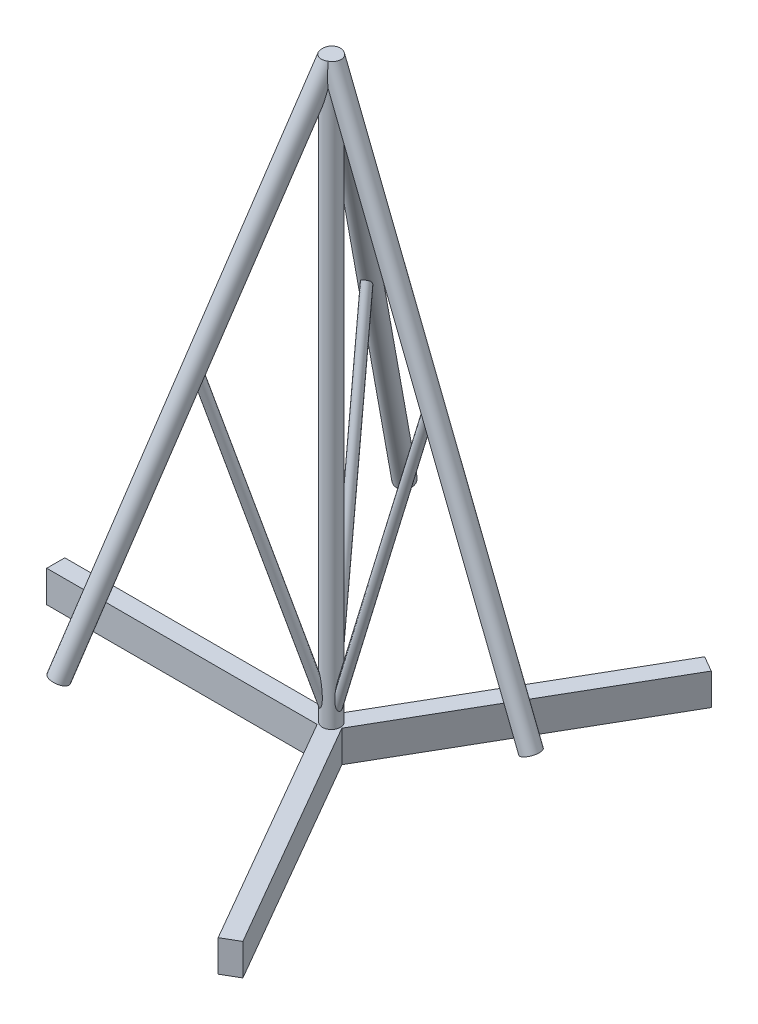
SolidWorks part; units mm, degrees
ref_plane "Front Plane" through (0, 0, 0) normal (0, 0, 1) x (1, 0, 0)
ref_plane "Top Plane" through (0, 0, 0) normal (0, 1, 0) x (1, 0, 0)
ref_plane "Right Plane" through (0, 0, 0) normal (1, 0, 0) x (0, 0, -1)
sketch3d "3DSketch1"
  line L0 (0, 0, 0) -> (0, 135, 0)
  line L1 (0, 135, 0) -> (44.1531, 23.4182, 0)
  line L2 (0, 7, 0) -> (22.0765, 79.2091, 0)
  point P6 (15.4502, 20.9988, 0)
  point P7 (0, 0, 0)
  point P8 (0, 0, 0)
  point P9 (0, 0, 0)
  point P10 (0, 0, 0)
  dimension "D1" = 7
  dimension "D2" = 135
  dimension "D3" = 120
  dimension "D4" = 17
sweep "Sweep1" add path "3DSketch1" circular profile diameter 4 parameters "D3"=4
sketch3d "3DSketch2"
  line L0 (0, 7, 0) -> (22.0765, 79.2091, 0) construction
  line L1 (0, 7, 0) -> (22.0765, 79.2091, 0)
sweep "Sweep2" add path "3DSketch2" circular profile diameter 2 parameters "D3"=2
ref_plane "Plane1" through (0, 150, 0) normal (0, 1, 0) x (1, 0, 0)
sketch "Sketch50" plane through (0, 150, 0) normal (0, 1, 0) x (1, 0, 0)
  circle A1 centre (0, 0) radius 5.4645
extrude "Cut-Extrude3" cut sketch "Sketch50" against normal up to vertex (15 mm away) up to point (0, 135, 0)
pattern_circular "CirPattern2" count 3 over 360 about axis through (0, 0, 0) along (0, 1, 0) of "Sweep1", "Sweep2", "Cut-Extrude3" reverse direction yes
sketch "Sketch90" plane through (0, 0, 0) normal (0, -1, 0) x (1, 0, 0)
  line L0 (1, 1.7321) -> (21.5, 37.2391) construction
  line L1 (44.1531, 2) -> (1.1547, 2) construction
  line L2 (28.7516, 53.7991) -> (32.2157, 51.7991)
  line L3 (1.7321, -1) -> (32.2157, 51.7991)
  line L4 (-1.7321, 1) -> (28.7516, 53.7991)
  line L5 (-1.7321, -1) -> (28.7516, -53.7991)
  line L6 (1.7321, 1) -> (32.2157, -51.7991)
  line L7 (0, 2) -> (-60.9672, 2)
  line L8 (0, -2) -> (-60.9672, -2)
  line L9 (32.2157, -51.7991) -> (28.7516, -53.7991)
  line L10 (-60.9672, 2) -> (-60.9672, -2)
  circle A0 centre (0, 0) radius 43 construction
  circle A1 centre (0, 0) radius 2 construction
  circle A3 centre (0, 0) radius 2
  circle A5 centre (0, 0) radius 61 construction
  point P13 (0, 0)
  point P24 (0, 0)
  point P26 (26.1666, 41.3219)
  point P27 (32.2186, 51.7973)
  circle M9 centre (0, 0) radius 2
  dimension "D1" = 60
  dimension "D2" = 3
extrude "Boss-Extrude1" add sketch "Sketch90" against normal blind 7 separate body contours L9 L6 L3 L8 L5 M9 | L8 L5 M9 | L7 L10 L8 L5 L4 M9 | L7 L4 M9 | L6 L3 M9 | L0 L6 L3 L2 M9 | A3 L0 L2 L4 L7 | A3 M9 region at (15.6611, 0, 27.1258) region at (-1.0336, 0, 1.7902) region at (-31.3221, 0, 0) region at (15.6611, 0, -27.1258) region at (2.0671, 0, 0) region at (0, 0, 0) region at (-1.0336, 0, -1.7902)
